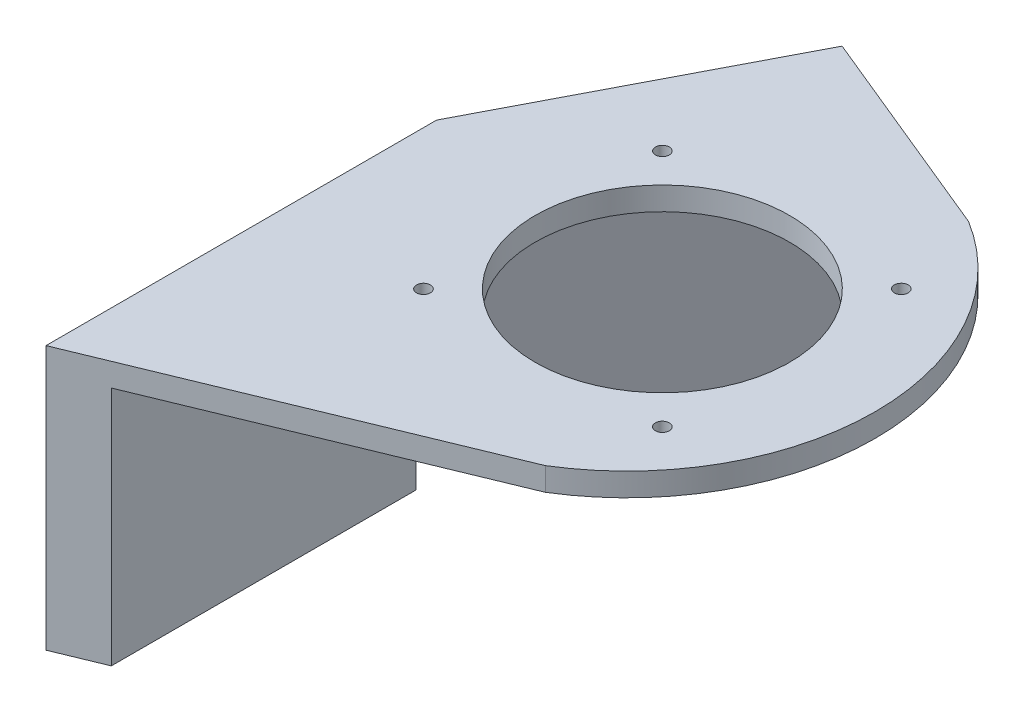
SolidWorks part; units mm, degrees
ref_plane "Front Plane" through (0, 0, 0) normal (0, 0, 1) x (1, 0, 0)
ref_plane "Top Plane" through (0, 0, 0) normal (0, 1, 0) x (1, 0, 0)
ref_plane "Right Plane" through (0, 0, 0) normal (1, 0, 0) x (0, 0, -1)
sketch "Sketch2" plane through (0, 0, 0) normal (0, 1, 0) x (1, 0, 0)
  line L10 (109.5, -38.6) -> (155.4807, -38.6) construction
  line L16 (104.5, -77.2) -> (142.7026, -61.4563)
  line L23 (109.5, -35) -> (123.6013, -7.8719) construction
  line L26 (104.5, 0) -> (104.5, -77.2) construction
  line L27 (109.5, -35) -> (104.5, -35) construction
  line L29 (104.5, -42.2) -> (109.5, -42.2) construction
  line L30 (109.5, -42.2) -> (109.5, -75.1394) construction
  line L31 (116.4903, -54.6) -> (148.4903, -22.6) construction
  line L36 (116.4903, -22.6) -> (148.4903, -54.6) construction
  line L37 (104.5, -35) -> (119.4834, -6.1748) construction
  line L38 (104.5, -35) -> (119.4834, -6.1748)
  line L39 (142.7026, -15.7437) -> (119.4834, -6.1748)
  line L40 (104.5, -35) -> (104.5, -77.2)
  arc A2 (142.7026, -15.7437) -> (142.7026, -61.4563) centre (128.65, -38.6) cw
  circle A3 centre (132.4903, -38.6) radius 13.75
  circle A4 centre (145.395, -25.6953) radius 0.75
  circle A5 centre (119.5856, -51.5047) radius 0.75
  circle A6 centre (119.5856, -25.6953) radius 0.75
  circle A7 centre (145.395, -51.5047) radius 0.75
  dimension "D3" = 35
  dimension "D5" = 32
  dimension "D9" = 18.25
  dimension "D1" = 35
  dimension "D2" = 5
  dimension "D4" = 5
  dimension "D6" = 32
extrude "Boss-Extrude1" add sketch "Sketch2" along normal blind 2.5
sketch "Sketch3" plane through (0, 0, 0) normal (0, -1, 0) x (1, 0, 0)
  line L11 (104.5, 42.2) -> (109.5, 42.2)
  line L12 (109.5, 42.2) -> (109.5, 75.1394)
  line L13 (109.5, 75.1394) -> (104.5, 77.2)
  line L14 (104.5, 77.2) -> (104.5, 42.2)
  line L15 (109.5, 35) -> (104.5, 35)
  line L16 (104.5, 35) -> (119.4834, 6.1748)
  line L17 (119.4834, 6.1748) -> (123.6013, 7.8719)
  line L18 (123.6013, 7.8719) -> (109.5, 35)
extrude "Boss-Extrude2" add sketch "Sketch3" along normal blind 26
sketch "Sketch5" plane through (104.5, 0, 0) normal (-1, 0, 0) x (0, 0, 1)
  line L0 (42.2, -26) -> (42.2, 0) construction
  line L1 (35, 0) -> (42.2, 0)
  line L2 (35, 0) -> (35, -21)
  line L3 (35, -21) -> (42.2, -21)
  line L4 (42.2, 0) -> (42.2, -21)
  line L5 (77.2, -26) -> (42.2, -26) construction
  dimension "D1" = 5
extrude "Boss-Extrude5" add sketch "Sketch5" against normal blind 5
